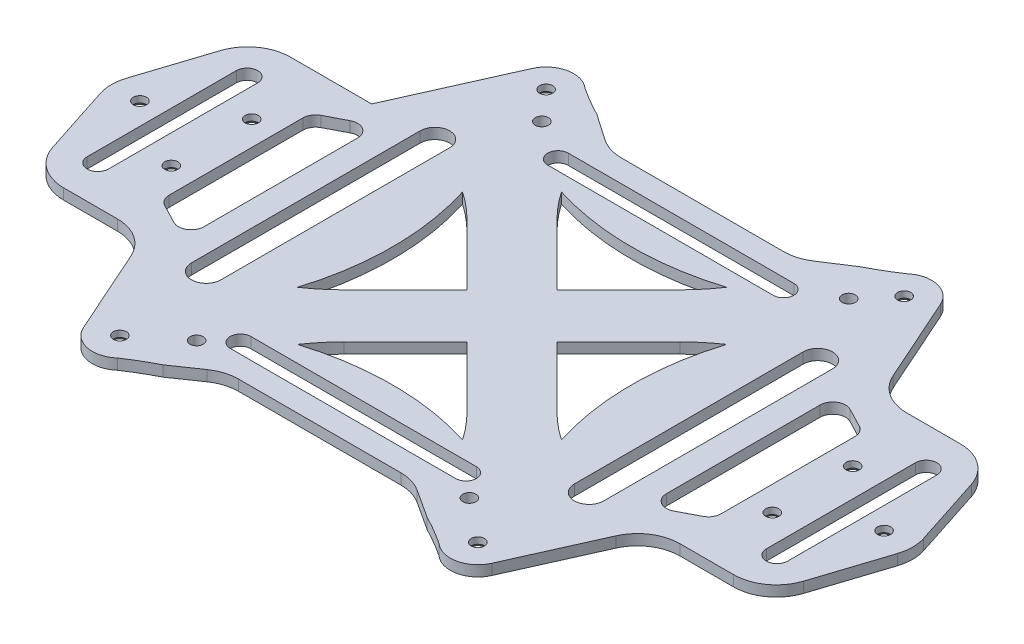
SolidWorks part; units mm, degrees
material "PPS"
ref_plane "前视基准面" through (0, 0, 0) normal (0, 0, 1) x (1, 0, 0)
ref_plane "上视基准面" through (0, 0, 0) normal (0, 1, 0) x (1, 0, 0)
ref_plane "右视基准面" through (0, 0, 0) normal (1, 0, 0) x (0, 0, -1)
sketch "参考" plane through (0, 0, 0) normal (0, 1, 0) x (1, 0, 0)
  line L3 (-133.7177, 0) -> (146.3754, 0) construction
  line L56 (0, 96.0639) -> (0, -115.1457) construction
  line L177 (114.5911, 7.4683) -> (114.5911, -7.4683)
  line L178 (114.5911, 7.4683) -> (43.1936, 17.6463)
  line L179 (114.5911, -7.4683) -> (43.1936, -17.6463)
  line L180 (-114.5911, -7.4683) -> (-43.1936, -17.6463)
  line L181 (-114.5911, 7.4683) -> (-114.5911, -7.4683)
  line L182 (-114.5911, 7.4683) -> (-43.1936, 17.6463)
  arc A18 (-37.7098, 54.831) -> (37.7098, 54.831) centre (0, 111.5317) ccw
  arc A20 (48.2756, 48.4632) -> (43.1936, 17.6463) centre (246.1791, 0) ccw
  arc A21 (48.2756, 48.4632) -> (37.7098, 54.831) centre (42, 50) ccw
  arc A22 (-37.7098, -54.831) -> (37.7098, -54.831) centre (0, -111.5317) cw
  arc A23 (48.2756, -48.4632) -> (43.1936, -17.6463) centre (246.1791, 0) cw
  arc A24 (48.2756, -48.4632) -> (37.7098, -54.831) centre (42, -50) cw
  arc A26 (-48.2756, -48.4632) -> (-37.7098, -54.831) centre (-42, -50) ccw
  arc A27 (-48.2756, -48.4632) -> (-43.1936, -17.6463) centre (-246.1791, 0) ccw
  arc A28 (-48.2756, 48.4632) -> (-37.7098, 54.831) centre (-42, 50) cw
  arc A30 (-48.2756, 48.4632) -> (-43.1936, 17.6463) centre (-246.1791, 0) cw
  dimension "D11" = 50
  dimension "D12" = 42
sketch "草图1" plane through (0, 0, 0) normal (0, 1, 0) x (1, 0, 0)
  line L0 (-160.1541, 0) -> (172.3115, 0) construction
  line L1 (0, 124.2182) -> (0, 50.8906) construction
  line L2 (79.6696, -17.5) -> (79.6696, 17.5) construction
  line L3 (77.1696, -17.5) -> (77.1696, 17.5)
  line L4 (82.1696, -17.5) -> (82.1696, 17.5)
  line L5 (-133.7177, 0) -> (146.3754, 0) construction
  line L6 (47.9, 52.6334) -> (59.525, 26.5883)
  line L7 (59.525, 26.5883) -> (85.8696, 26.5883)
  line L8 (85.8696, 26.5883) -> (94.5058, 0)
  line L9 (59.525, -26.5883) -> (85.8696, -26.5883)
  line L10 (47.9, -52.6334) -> (59.525, -26.5883)
  line L11 (85.8696, -26.5883) -> (94.5058, 0)
  line L12 (-47.9, -52.6334) -> (-59.525, -26.5883)
  line L13 (-59.525, -26.5883) -> (-85.8696, -26.5883)
  line L14 (-85.8696, -26.5883) -> (-94.5058, 0)
  line L15 (-85.8696, 26.5883) -> (-94.5058, 0)
  line L16 (-47.9, 52.6334) -> (-59.525, 26.5883)
  line L17 (-59.525, 26.5883) -> (-85.8696, 26.5883)
  line L18 (-79.6696, -17.5) -> (-79.6696, 17.5) construction
  line L19 (-77.1696, -17.5) -> (-77.1696, 17.5)
  line L20 (-82.1696, -17.5) -> (-82.1696, 17.5)
  line L21 (-24.996, 14.4296) -> (-10.5664, 0)
  line L22 (14.4296, 24.996) -> (0, 10.5664)
  line L23 (-24.996, -14.4296) -> (-10.5664, 0)
  line L24 (-14.4296, 24.996) -> (0, 10.5664)
  line L25 (0, 96.0639) -> (0, -115.1457) construction
  line L26 (24.996, -14.4296) -> (10.5664, 0)
  line L27 (24.996, 14.4296) -> (10.5664, 0)
  line L28 (-14.4296, -24.996) -> (0, -10.5664)
  line L29 (14.4296, -24.996) -> (0, -10.5664)
  line L30 (44.9192, -26.8293) -> (44.9192, 26.8293) construction
  line L31 (41.4687, -26.8293) -> (41.4687, 26.8293)
  line L32 (48.3697, -26.8293) -> (48.3697, 26.8293)
  line L33 (-26.4535, -37.2441) -> (26.4535, -37.2441) construction
  line L34 (-26.4535, -34.8191) -> (26.4535, -34.8191)
  line L35 (-26.4535, -39.6691) -> (26.4535, -39.6691)
  line L36 (-26.4535, 37.2441) -> (26.4535, 37.2441) construction
  line L37 (-26.4535, 34.8191) -> (26.4535, 34.8191)
  line L38 (-26.4535, 39.6691) -> (26.4535, 39.6691)
  line L39 (-44.9192, -26.8293) -> (-44.9192, 26.8293) construction
  line L40 (-41.4687, -26.8293) -> (-41.4687, 26.8293)
  line L41 (-48.3697, -26.8293) -> (-48.3697, 26.8293)
  line L44 (0, -44.9191) -> (21.7864, -44.9191)
  line L45 (21.7864, -44.9191) -> (30.9782, -50.8906)
  line L46 (0, -44.9191) -> (-22.3179, -44.9191)
  line L47 (-22.3179, -44.9191) -> (-30.9782, -50.8906)
  line L48 (0, -50.8906) -> (0, -143.4382) construction
  line L49 (21.7864, 44.9191) -> (30.9782, 50.8906)
  line L50 (0, 44.9191) -> (21.7864, 44.9191)
  line L51 (0, 44.9191) -> (-22.3179, 44.9191)
  line L52 (-22.3179, 44.9191) -> (-30.9782, 50.8906)
  line L53 (0, 44.9191) -> (0, -44.9191) construction
  circle A6 centre (42, 50) radius 1.55
  circle A7 centre (42, -50) radius 1.55
  circle A8 centre (-42, -50) radius 1.55
  circle A9 centre (-42, 50) radius 1.55
  circle A10 centre (36, 43) radius 1.55
  circle A11 centre (32, -42) radius 1.55
  circle A12 centre (-32, -42) radius 1.55
  circle A13 centre (-36, 43) radius 1.55
  arc A14 (47.9, 52.6334) -> (37.7098, 54.831) centre (42, 50) ccw
  arc A15 (-37.7098, 54.831) -> (-30.9782, 50.8906) centre (0, 111.5317) ccw
  arc A18 (77.1696, -17.5) -> (82.1696, -17.5) centre (79.6696, -17.5) ccw
  arc A19 (82.1696, 17.5) -> (77.1696, 17.5) centre (79.6696, 17.5) ccw
  circle A20 centre (70.5, 9.4358) radius 1.55
  circle A21 centre (70.5, -9.4358) radius 1.55
  circle A22 centre (-70.5, -9.4358) radius 1.55
  circle A23 centre (-70.5, 9.4358) radius 1.55
  circle A24 centre (87.3, 0) radius 1.55
  arc A25 (48.2756, 48.4632) -> (37.7098, 54.831) centre (42, 50) ccw construction
  arc A26 (47.9, -52.6334) -> (37.7098, -54.831) centre (42, -50) cw
  arc A27 (-37.7098, -54.831) -> (-30.9782, -50.8906) centre (0, -111.5317) cw
  arc A28 (-47.9, 52.6334) -> (-37.7098, 54.831) centre (-42, 50) cw
  arc A29 (-77.1696, -17.5) -> (-82.1696, -17.5) centre (-79.6696, -17.5) cw
  arc A30 (-82.1696, 17.5) -> (-77.1696, 17.5) centre (-79.6696, 17.5) cw
  circle A31 centre (-87.3, 0) radius 1.55
  arc A32 (-47.9, -52.6334) -> (-37.7098, -54.831) centre (-42, -50) ccw
  arc A33 (-24.996, 14.4296) -> (-30.9782, 19.3706) centre (-53.9062, -14.4807) ccw
  arc A34 (-24.996, -14.4296) -> (-30.9782, -19.3706) centre (-53.9062, 14.4807) cw
  arc A35 (-30.9782, -19.3706) -> (-30.9782, 19.3706) centre (-93.0146, 0) ccw
  arc A36 (-14.4296, 24.996) -> (-19.3706, 30.9782) centre (14.4807, 53.9062) cw
  arc A37 (-19.3706, 30.9782) -> (19.3706, 30.9782) centre (0, 93.0146) ccw
  arc A38 (14.4296, 24.996) -> (19.3706, 30.9782) centre (-14.4807, 53.9062) ccw
  arc A39 (24.996, 14.4296) -> (30.9782, 19.3706) centre (53.9062, -14.4807) cw
  arc A40 (30.9782, 19.3706) -> (30.9782, -19.3706) centre (93.0146, 0) ccw
  arc A41 (24.996, -14.4296) -> (30.9782, -19.3706) centre (53.9062, 14.4807) ccw
  arc A42 (14.4296, -24.996) -> (19.3706, -30.9782) centre (-14.4807, -53.9062) cw
  arc A43 (19.3706, -30.9782) -> (-19.3706, -30.9782) centre (0, -93.0146) ccw
  arc A44 (-14.4296, -24.996) -> (-19.3706, -30.9782) centre (14.4807, -53.9062) ccw
  arc A45 (41.4687, -26.8293) -> (48.3697, -26.8293) centre (44.9192, -26.8293) ccw
  arc A46 (48.3697, 26.8293) -> (41.4687, 26.8293) centre (44.9192, 26.8293) ccw
  arc A47 (-26.4535, -34.8191) -> (-26.4535, -39.6691) centre (-26.4535, -37.2441) ccw
  arc A48 (26.4535, -39.6691) -> (26.4535, -34.8191) centre (26.4535, -37.2441) ccw
  arc A49 (-26.4535, 34.8191) -> (-26.4535, 39.6691) centre (-26.4535, 37.2441) cw
  arc A50 (26.4535, 39.6691) -> (26.4535, 34.8191) centre (26.4535, 37.2441) cw
  arc A51 (-41.4687, -26.8293) -> (-48.3697, -26.8293) centre (-44.9192, -26.8293) cw
  arc A52 (-48.3697, 26.8293) -> (-41.4687, 26.8293) centre (-44.9192, 26.8293) cw
  arc A53 (30.9782, 50.8906) -> (37.7098, 54.831) centre (0, 111.5317) ccw
  arc A54 (30.9782, -50.8906) -> (37.7098, -54.831) centre (0, -111.5317) cw
  point P30 (79.6696, 0)
  point P63 (44.9192, 0)
  point P78 (-79.6696, 0)
  point P98 (0, 0)
  point P116 (0, -37.2441)
  point P129 (0, 37.2441)
  point P136 (-44.9192, 0)
  dimension "D1" = 50
  dimension "D3" = 3.1
  dimension "D8" = 2.5
  dimension "D10" = 3.1
  dimension "D12" = 3.1
  dimension "D15" = 37.2441
  dimension "D2" = 42
  dimension "D4" = 36
  dimension "D5" = 32
  dimension "D6" = 42
  dimension "D7" = 43
  dimension "D9" = 35
  dimension "D11" = 70.5
  dimension "D13" = 87.3
  dimension "D14" = 4
  dimension "D16" = 5.25
  dimension "D17" = 4.85
extrude "凸台-拉伸1" add sketch "草图1" along normal blind 2.5
chamfer "倒角2" distance 1 angle 45 10 edges at (-70.5, 0, 10.9858) (-70.5, 0, -10.9858) (70.5, 0, 7.8858) (70.5, 0, -7.8858) (-87.3, 0, -1.55) (87.3, 0, 1.55) (-42, 0, 51.55) (42, 0, 48.45) (-42, 0, -51.55) (42, 0, -48.45)
sketch "减重草图镂空-如果影响结构强度则取消" plane through (0, 0, 0) normal (0, -1, 0) x (1, 0, 0)
  line L0 (0, 0) -> (0, 77.9145) construction
  line L1 (0, 0) -> (127.571, 0) construction
  line L2 (-64.75, 17.5) -> (-54.25, 22.966)
  line L3 (-54.25, 22.966) -> (-54.25, -22.966)
  line L4 (-54.25, -22.966) -> (-64.75, -17.5)
  line L5 (-64.75, -17.5) -> (-64.75, 17.5)
  line L6 (54.25, -22.966) -> (64.75, -17.5)
  line L7 (54.25, 22.966) -> (54.25, -22.966)
  line L8 (64.75, 17.5) -> (54.25, 22.966)
  line L9 (64.75, -17.5) -> (64.75, 17.5)
  circle A1 centre (-70.5, 9.4358) radius 1.55 construction
  dimension "D1" = 5.75
  dimension "D2" = 54.25
  dimension "D3" = 62.5
  dimension "D4" = 17.5
extrude "减重-如果影响结构强度则取消" cut sketch "减重草图镂空-如果影响结构强度则取消" against normal through all
fillet "圆角2" radius 3 8 edges at (64.75, 1.25, 17.5) (64.75, 1.25, -17.5) (54.25, 1.25, -22.966) (54.25, 1.25, 22.966) (-54.25, 1.25, -22.966) (-64.75, 1.25, -17.5) (-64.75, 1.25, 17.5) (-54.25, 1.25, 22.966)
fillet "圆角3" radius 10 13 edges at (21.7864, 1.25, 44.9191) (-22.3179, 1.25, 44.9191) (21.7864, 1.25, -44.9191) (-22.3179, 1.25, -44.9191) (59.525, 1.25, -26.5883) (85.8696, 1.25, -26.5883) (94.5058, 1.25, 0) (85.8696, 1.25, 26.5883) (59.525, 1.25, 26.5883) (-59.525, 1.25, 26.5883) (-85.8696, 1.25, -26.5883) (-94.5058, 1.25, 0) (-85.8696, 1.25, 26.5883)
